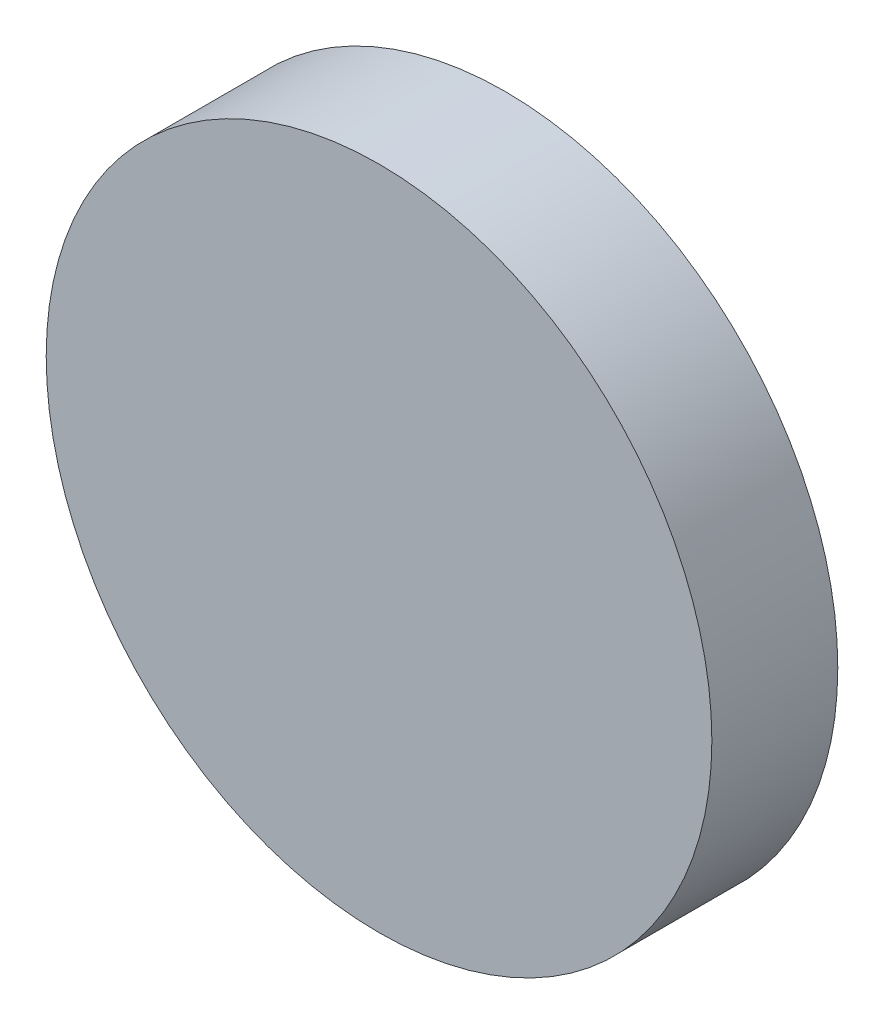
SolidWorks part; units mm, degrees
ref_plane "Alzado" through (0, 0, 0) normal (0, 0, 1) x (1, 0, 0)
ref_plane "Planta" through (0, 0, 0) normal (0, 1, 0) x (1, 0, 0)
ref_plane "Vista lateral" through (0, 0, 0) normal (1, 0, 0) x (0, 0, -1)
sketch "Croquis1" plane through (0, 0, 0) normal (0, 0, 1) x (1, 0, 0)
  line L1 (-0.75, 2.9047) -> (0.75, 2.9047)
  line L2 (-0.75, 2.9047) -> (-0.75, -2.9047)
  line L3 (-0.75, -2.9047) -> (0.75, -2.9047)
  line L4 (0.75, 2.9047) -> (0.75, -2.9047)
  circle A0 centre (0, 0) radius 9.25
  circle A1 centre (0, 0) radius 3
  point P8 (0, 2.9047)
  dimension "D1" = 18.5
  dimension "D2" = 6
  dimension "D3" = 1.5
extrude "Saliente-Extruir1" add sketch "Croquis1" along normal blind 2.5 contours A0 A1 | L2 A1 | L4 A1 | L4 L1 L2 L3 | L3 A1 | L1 A1 region at (0, 2.9429, 0) region at (0, 0, 0) region at (-1.6871, 0, 0) region at (1.6871, 0, 0) region at (0, -2.9429, 0) region at (-8.9884, 0, 0)
extrude "Saliente-Extruir2" add sketch "Croquis1<4>" against normal blind 5 contours L4 L1 L2 L3 | L1 A1 | L3 A1 region at (0, 2.9429, 0) region at (0, 0, 0) region at (0, -2.9429, 0)
sketch "Croquis1<4>" plane through (0, 0, 0) normal (0, 0, 1) x (1, 0, 0) same geometry as "Croquis1"
extrude "Saliente-Extruir3" add sketch "Croquis1<5>" against normal blind 1 contours A0 A1 region at (-8.9884, 0, 0)
sketch "Croquis1<5>" plane through (0, 0, 0) normal (0, 0, 1) x (1, 0, 0) same geometry as "Croquis1"
sketch "Croquis2" plane through (0.75, 0, 0) normal (1, 0, 0) x (0, 0, -1)
  circle A0 centre (3.1, 0) radius 1.25
  point P2 (0, 0)
  dimension "D2" = 2.5
  dimension "D1" = 3.1
extrude "Cortar-Extruir1" cut sketch "Croquis2" against normal up to next
